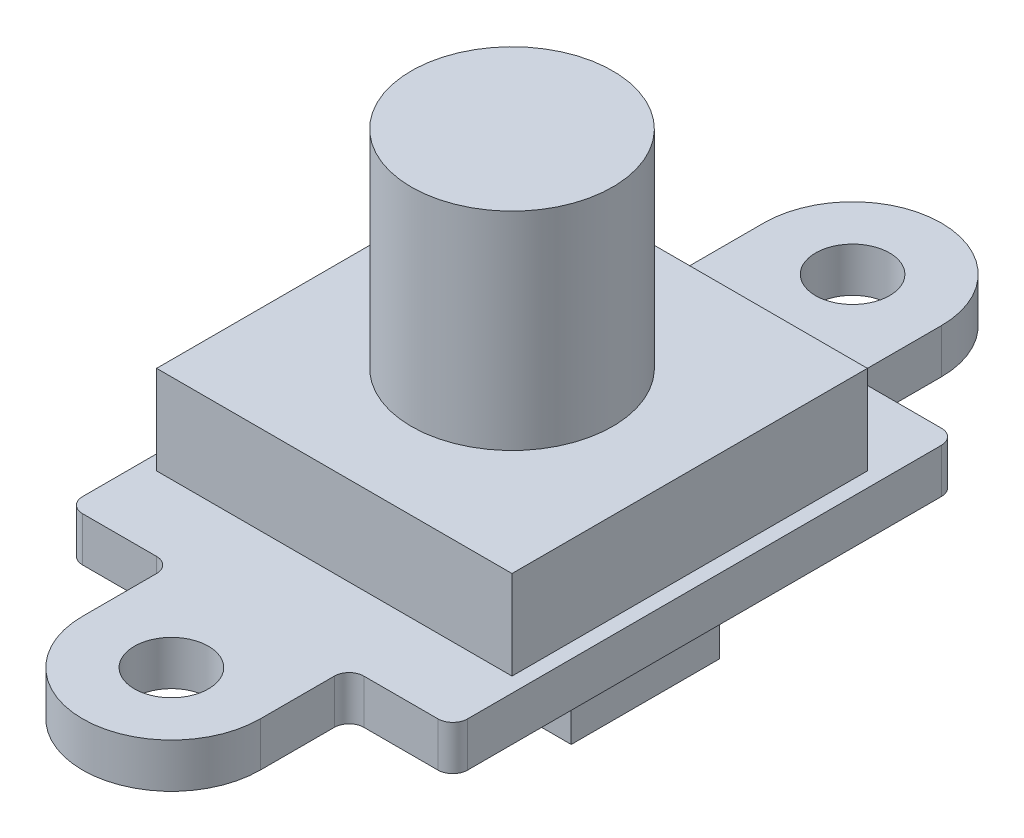
SolidWorks part; units mm, degrees
ref_plane "前视基准面" through (0, 0, 0) normal (0, 0, 1) x (1, 0, 0)
ref_plane "上视基准面" through (0, 0, 0) normal (0, 1, 0) x (1, 0, 0)
ref_plane "右视基准面" through (0, 0, 0) normal (1, 0, 0) x (0, 0, -1)
other "Configuration Table"
ref_axis "基准轴1" through (0, -46.8641, 0) along (0, 1, 0)
sketch "草图1" plane through (0, 0, 0) normal (0, 1, 0) x (1, 0, 0)
  line L2 (-3, -11.5) -> (-3, -8.5)
  line L3 (-6.5, 8.5) -> (6.5, 8.5)
  line L4 (-6.5, 8.5) -> (-6.5, -8.5)
  line L5 (-6.5, -8.5) -> (6.5, -8.5)
  line L6 (6.5, 8.5) -> (6.5, -8.5)
  line L7 (3, -11.5) -> (3, -8.5)
  line L8 (0, -11.5) -> (0, 11.5) construction
  line L9 (3, 11.5) -> (3, 8.5)
  line L10 (-3, 11.5) -> (-3, 8.5)
  circle A3 centre (0, -11.5) radius 1.25
  circle A4 centre (0, -11.5) radius 3
  circle A5 centre (0, 11.5) radius 1.25
  circle A6 centre (0, 11.5) radius 3
  point P12 (0, 0)
  dimension "D1" = 2.5
  dimension "D2" = 6
  dimension "D3" = 17
  dimension "D4" = 13
extrude "凸台-拉伸-PCB板" add sketch "草图1" along normal blind 1.5 contours L8 L5 L6 L3 | L5 L8 L3 L4 | A4 L5 L2 | A4 L7 L5 | A3 A4 | A6 L10 L3 | A6 L3 L9 | A6 A5 region at (-2.0613, 0, 9.4387) region at (-2.3299, 0, 9.1701) region at (-3.25, 0, 0) region at (2.3299, 0, 9.1701) region at (3.25, 0, 0) region at (2.3299, 0, -9.1701) region at (-2.3299, 0, -9.1701) region at (-2.0613, 0, -9.4387)
sketch "草图6" plane through (0, 0, 0) normal (0, -1, 0) x (1, 0, 0)
  line L1 (4.5, 2.5) -> (-0.5, 2.5)
  line L2 (4.5, 2.5) -> (4.5, -2.5)
  line L3 (4.5, -2.5) -> (-0.5, -2.5)
  line L4 (-0.5, 2.5) -> (-0.5, -2.5)
  line L5 (0, 0) -> (-0.5, 0) construction
  line L10 (6.5, -8.5) -> (6.5, 8.5) construction
  point P6 (-0.5, 0)
  dimension "D1" = 5
  dimension "D2" = 2
  dimension "D3" = 5
extrude "凸台-拉伸2" add sketch "草图6" along normal blind 3
sketch "草图3" plane through (0, 1.5, 0) normal (0, 1, 0) x (1, 0, 0)
  line L6 (-6, 6) -> (6, 6)
  line L7 (-6, 6) -> (-6, -6)
  line L8 (-6, -6) -> (6, -6)
  line L9 (6, 6) -> (6, -6)
  line L10 (-6, 6) -> (6, -6) construction
  line L11 (-6, -6) -> (6, 6) construction
  point P0 (0, 0)
  dimension "D1" = 12
extrude "凸台-拉伸-Button-底座" add sketch "草图3" along normal blind 3
sketch "草图7" plane through (0, 4.5, 0) normal (0, 1, 0) x (1, 0, 0)
  circle A0 centre (0, 0) radius 3.4
  dimension "D1" = 6.8
extrude "凸台-拉伸3" add sketch "草图7" along normal blind 7
fillet "圆角1" radius 0.5 8 edges at (-6.5, 0.75, -8.5) (-3, 0.75, 8.5) (-6.5, 0.75, 8.5) (3, 0.75, 8.5) (6.5, 0.75, -8.5) (6.5, 0.75, 8.5) (-3, 0.75, -8.5) (3, 0.75, -8.5)
